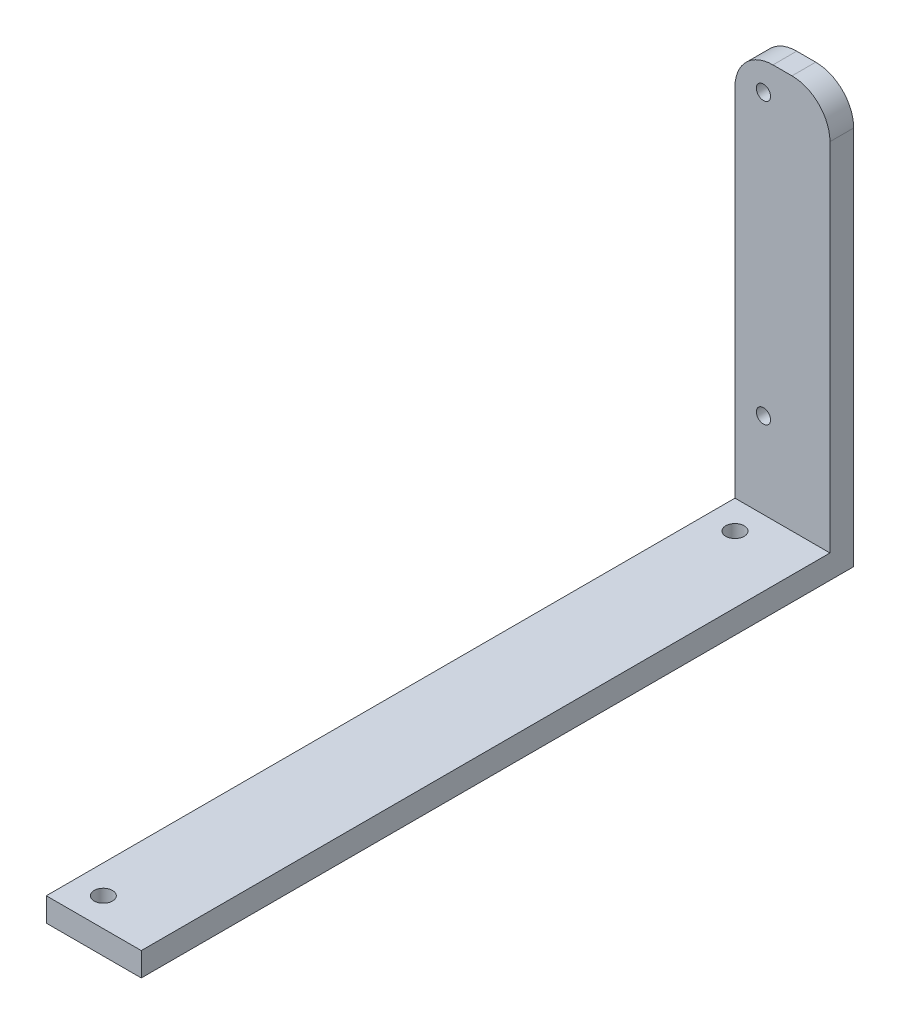
SolidWorks part; units mm, degrees
ref_plane "Front Plane" through (0, 0, 0) normal (0, 0, 1) x (1, 0, 0)
ref_plane "Top Plane" through (0, 0, 0) normal (0, 1, 0) x (1, 0, 0)
ref_plane "Right Plane" through (0, 0, 0) normal (1, 0, 0) x (0, 0, -1)
sketch "Sketch1" plane through (0, 0, 0) normal (0, 0, 1) x (1, 0, 0)
  line L1 (0, 0) -> (20, 0)
  line L2 (0, 0) -> (0, 88)
  line L3 (0, 88) -> (20, 88)
  line L4 (20, 0) -> (20, 88)
  circle A0 centre (6, 82) radius 1.5
  circle A1 centre (6, 23) radius 1.5
  dimension "D3" = 3
  dimension "D1" = 88
  dimension "D2" = 20
  dimension "D4" = 6
  dimension "D5" = 6
  dimension "D6" = 59
extrude "Boss-Extrude1" add sketch "Sketch1" along normal blind 5
sketch "Sketch2" plane through (0, 0, 5) normal (0, 0, 1) x (1, 0, 0)
  line L0 (20, 0) -> (20, 88) construction
  line L1 (0, 0) -> (20, 0)
  line L2 (0, 0) -> (0, 5)
  line L3 (0, 5) -> (20, 5)
  line L4 (20, 0) -> (20, 5)
  dimension "D1" = 5
extrude "Boss-Extrude2" add sketch "Sketch2" along normal blind 145
fillet "Fillet1" radius 8 2 edges at (20, 88, 2.5) (0, 88, 2.5)
sketch "Sketch3" plane through (0, 5, 0) normal (0, 1, 0) x (1, 0, 0)
  line L0 (20, -150) -> (0, -150) construction
  line L1 (20, -5) -> (0, -5) construction
  line L2 (0, -150) -> (0, -5) construction
  circle A0 centre (6, -144) radius 1.9394
  circle A1 centre (6, -11) radius 1.9394
  dimension "D1" = 6
  dimension "D2" = 6
  dimension "D3" = 6
extrude "Cut-Extrude1" cut sketch "Sketch3" against normal through all
